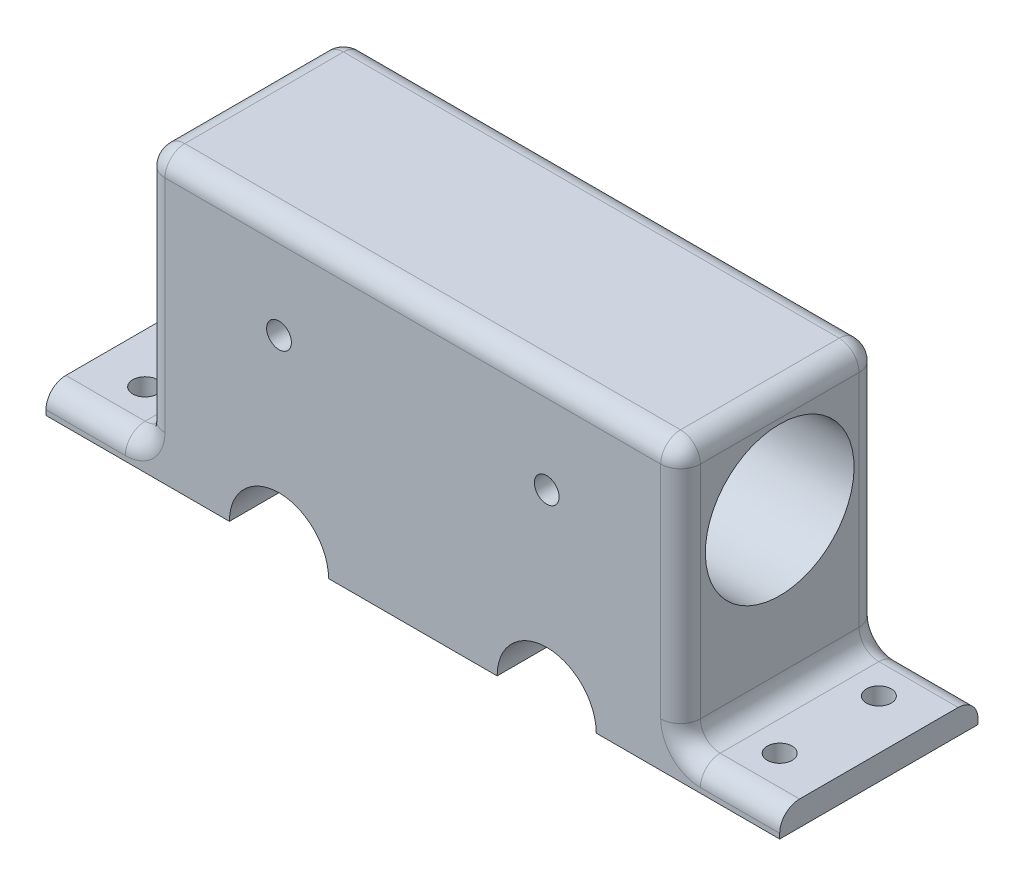
SolidWorks part; units mm, degrees
ref_plane "Front Plane" through (0, 0, 0) normal (0, 0, 1) x (1, 0, 0)
ref_plane "Top Plane" through (0, 0, 0) normal (0, 1, 0) x (1, 0, 0)
ref_plane "Right Plane" through (0, 0, 0) normal (1, 0, 0) x (0, 0, -1)
sketch "Sketch1" plane through (0, 0, 0) normal (0, 0, 1) x (1, 0, 0)
  line L6 (-10.795, 0) -> (10.795, 0)
  line L7 (10.795, 0) -> (23.495, 0) construction
  line L8 (23.495, 0) -> (46.99, 0)
  line L9 (46.99, 0) -> (46.99, 3.175)
  line L10 (46.99, 3.175) -> (36.83, 3.175)
  line L11 (34.29, 5.715) -> (34.29, 36.5125)
  line L12 (34.29, 36.5125) -> (-34.29, 36.5125)
  line L13 (0, 36.5125) -> (0, 0) construction
  line L14 (-10.795, 0) -> (-23.495, 0) construction
  line L19 (-34.29, 5.715) -> (-34.29, 36.5125)
  line L20 (-46.99, 3.175) -> (-36.83, 3.175)
  line L21 (-46.99, 0) -> (-46.99, 3.175)
  line L22 (-23.495, 0) -> (-46.99, 0)
  arc A0 (10.795, 0) -> (23.495, 0) centre (17.145, 0) cw
  arc A2 (36.83, 3.175) -> (34.29, 5.715) centre (36.83, 5.715) cw
  arc A3 (-36.83, 3.175) -> (-34.29, 5.715) centre (-36.83, 5.715) ccw
  arc A4 (-10.795, 0) -> (-23.495, 0) centre (-17.145, 0) ccw
  point P18 (34.29, 3.175)
  point P21 (-34.29, 3.175)
  dimension "D1" = 6.35
  dimension "D7" = 2.54
  dimension "D2" = 17.145
  dimension "D4" = 12.7
  dimension "D5" = 3.175
  dimension "D6" = 33.3375
  dimension "D3" = 34.29
extrude "Boss-Extrude1" add sketch "Sketch1" along normal blind 25.4
sketch "Sketch2" plane through (0, 3.175, 0) normal (0, 1, 0) x (1, 0, 0)
  line L0 (40.64, -37.966) -> (40.64, 12.566) construction
  line L3 (40.64, -12.7) -> (34.29, -12.7) construction
  line L4 (0, 0) -> (0, -25.4) construction
  line L5 (34.29, -25.4) -> (-34.29, -25.4) construction
  line L7 (34.29, -25.4) -> (34.29, 0) construction
  circle A0 centre (40.64, -6.35) radius 1.5875
  circle A1 centre (40.64, -19.05) radius 1.5875
  circle A2 centre (-40.64, -6.35) radius 1.5875
  circle A3 centre (-40.64, -19.05) radius 1.5875
  dimension "D1" = 3.175
  dimension "D2" = 6.35
  dimension "D3" = 6.35
extrude "Cut-Extrude1" cut sketch "Sketch2" against normal through all
sketch "Sketch3" plane through (34.29, 0, 0) normal (1, 0, 0) x (0, 0, -1)
  line L0 (-12.7, 36.5125) -> (-12.7, 3.175) construction
  line L1 (-25.4, 36.5125) -> (0, 36.5125) construction
  line L2 (-25.4, 3.175) -> (0, 3.175) construction
  circle A0 centre (-12.7, 23.8125) radius 9.525
  dimension "D1" = 19.05
  dimension "D2" = 12.7
extrude "Cut-Extrude2" cut sketch "Sketch3" against normal through all
sketch "Sketch4" plane through (0, 0, 25.4) normal (0, 0, 1) x (1, 0, 0)
  line L0 (0, 0) -> (0, 36.5125) construction
  line L1 (-10.795, 0) -> (10.795, 0) construction
  line L2 (34.29, 36.5125) -> (-34.29, 36.5125) construction
  line L3 (17.145, 23.8125) -> (-17.145, 23.8125) construction
  circle A0 centre (17.145, 23.8125) radius 1.5875
  circle A1 centre (-17.145, 23.8125) radius 1.5875
  point P9 (0, 23.8125)
  dimension "D2" = 17.145
  dimension "D3" = 3.175
  dimension "D1" = 12.7
extrude "Cut-Extrude3" cut sketch "Sketch4" against normal through all
fillet "Fillet1" radius 2.54 16 edges at (41.91, 3.175, 0) (35.0339, 3.9189, 0) (41.91, 3.175, 25.4) (35.0339, 3.9189, 25.4) (34.29, 21.1137, 0) (34.29, 21.1137, 25.4) (-41.91, 3.175, 0) (-35.0339, 3.9189, 0) (-41.91, 3.175, 25.4) (-35.0339, 3.9189, 25.4) (0, 36.5125, 0) (0, 36.5125, 25.4) (-34.29, 36.5125, 12.7) (-34.29, 21.1137, 0) (-34.29, 21.1137, 25.4) (34.29, 36.5125, 12.7)
equation "\"span\" = 48"
equation "\"wing_chord\"= 9"
equation "\"fuse_len\"= 15"
equation "\"fuse_height\"= 5"
equation "\"fuse_wid\"= 5"
equation "\"foam_t\"= 0.1875"
equation "\"main_spar_len\"= 36"
equation "\"x_fuse_to_wing\"= 3"
equation "\"x_cg_from_le\"= 2.25"
equation "\"boom_len\"= 36"
equation "\"wing_spar_d\"= 0.5"
equation "\"wing_spar_spacing\"= 1.35"
equation "\"D1@Sketch1\"=\"wing_spar_d\"/2"
equation "\"D2@Sketch1\"=\"wing_spar_spacing\"/2"
equation "\"wing_spar_l\"= 48"
equation "\"wing_mount_l\" = 2.5"
equation "\"D1@Boss-Extrude1\"=\"boom_mount_l\""
equation "\"D2@Sketch2\"=\"boom_mount_l\"/4"
equation "\"boom_d\"= 0.75"
equation "\"D1@Sketch3\"=\"boom_d\""
equation "\"D2@Sketch3\"=\"boom_d\"/2 + .125"
equation "\"D6@Sketch1\"=\"boom_d\"*1.75"
equation "\"D1@Sketch4\"= \"boom_d\"/2 + 1/8"
equation "\"D2@Sketch4\"= \"wing_spar_spacing\"/2"
equation "\"D3@Sketch1\"= \"wing_spar_spacing\""
equation "\"wing_angle\"= 1.5"
equation "\"boom_mount_l\"= 1"
equation "\"vstab_span\"= 6.5"
equation "\"hstab_span\"= 15.25"
equation "\"tail_chord\"= 5"
